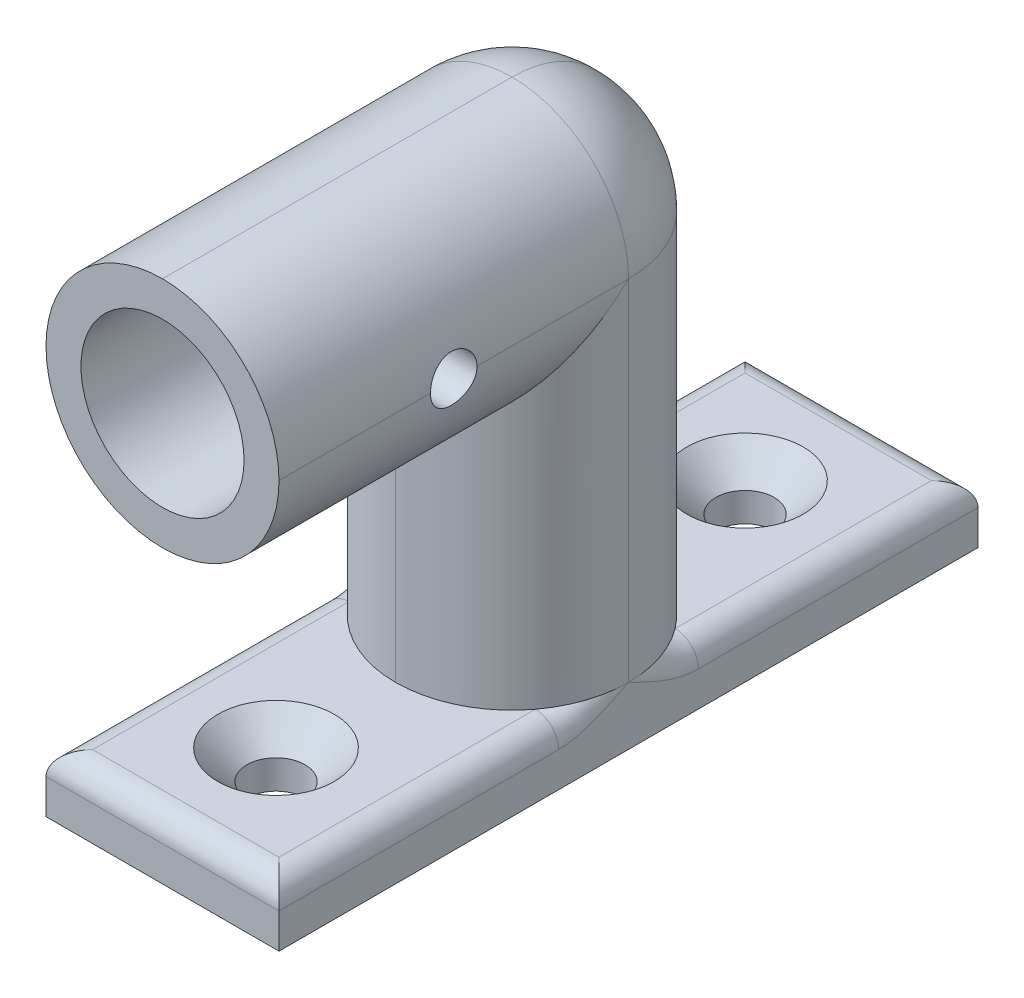
SolidWorks part; units mm, degrees
ref_plane "Front Plane" through (0, 0, 0) normal (0, 0, 1) x (1, 0, 0)
ref_plane "Top Plane" through (0, 0, 0) normal (0, 1, 0) x (1, 0, 0)
ref_plane "Right Plane" through (0, 0, 0) normal (1, 0, 0) x (0, 0, -1)
sketch "Sketch1" plane through (0, 0, 0) normal (1, 0, 0) x (0, 0, -1)
  line L0 (-20, 20) -> (-20, 10)
  line L1 (-20, 10) -> (-10, 10)
  line L2 (0, 0) -> (0, 20)
  line L3 (0, 20) -> (-20, 20)
  line L4 (-10, 10) -> (-10, 0)
  line L5 (-10, 0) -> (-20, 0)
  line L6 (-20, 0) -> (-20, -2.4922)
  line L7 (-20, -2.4922) -> (10, -2.4922)
  line L8 (10, -2.4922) -> (10, 0)
  line L9 (10, 0) -> (0, 0)
  dimension "D1" = 10
  dimension "D2" = 10
  dimension "D3" = 20
extrude "Boss-Extrude1" add sketch "Sketch1" along normal blind 10
sketch "Sketch2" plane through (0, 0, 20) normal (0, 0, 1) x (1, 0, 0)
  line L0 (10, 20) -> (0, 20) construction
  line L1 (0, 20) -> (0, 10) construction
  circle A0 centre (5, 15) radius 3.5
  point P2 (5, 20)
  dimension "D1" = 7
  dimension "D2" = 5
  dimension "D3" = 5
extrude "Cut-Extrude1" cut sketch "Sketch2" against normal blind 10
fillet "Fillet1" radius 5 8 edges at (0, 5, 10) (0, 10, 15) (0, 10, 0) (0, 20, 10) (10, 10, 0) (10, 5, 10) (10, 10, 15) (10, 20, 10)
sketch "Sketch3" plane through (0, -2.4922, 0) normal (0, -1, 0) x (1, 0, 0)
  line L0 (10, 20) -> (0, 20) construction
  line L1 (10, 5) -> (0, 5) construction
  line L2 (10, 20) -> (10, -10) construction
  line L3 (0, 20) -> (0, -10) construction
  line L4 (10, -10) -> (0, -10) construction
  circle A0 centre (4.8722, 15) radius 1.25
  circle A1 centre (5, -5) radius 1.25
  dimension "D2" = 5
  dimension "D4" = 2.5
  dimension "D5" = 2.5
  dimension "D1" = 5
  dimension "D3" = 5
extrude "Cut-Extrude2" cut sketch "Sketch3" against normal blind 10
chamfer "Chamfer1" distance 1.25 angle 45 2 edges at (5, 0, -6.25) (4.8722, 0, 13.75)
sketch "Sketch4" plane through (0, 0, 0) normal (1, 0, 0) x (0, 0, -1)
  line L0 (-5, 15) -> (-20, 15) construction
  circle A0 centre (-12.5, 15) radius 1
extrude "Cut-Extrude3" cut sketch "Sketch4" along normal blind 10
fillet "Fillet2" radius 1 6 edges at (0, 0, 12.5) (10, 0, -2.5) (5, 0, -10) (0, 0, -2.5) (5, 0, 20) (10, 0, 12.5)
